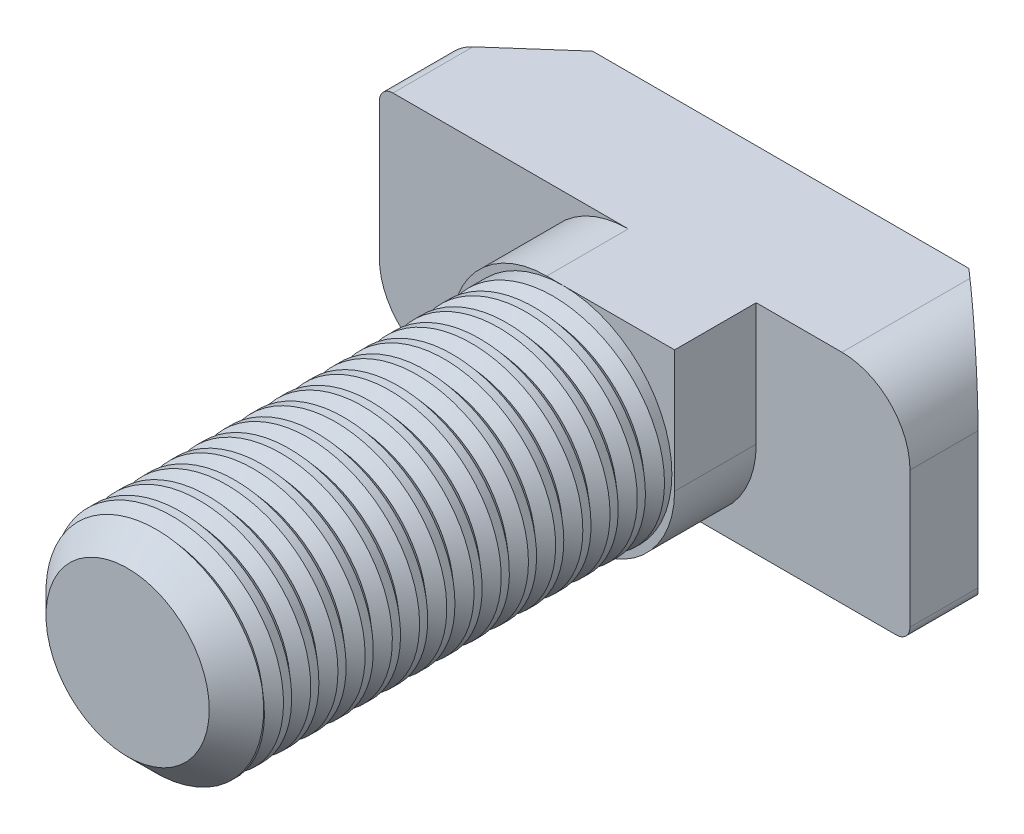
SolidWorks part; units mm, degrees
ref_plane "前视基准面" through (0, 0, 0) normal (0, 0, 1) x (1, 0, 0)
ref_plane "上视基准面" through (0, 0, 0) normal (0, 1, 0) x (1, 0, 0)
ref_plane "右视基准面" through (0, 0, 0) normal (1, 0, 0) x (0, 0, -1)
sketch "草图1" plane through (0, 0, 0) normal (0, 0, 1) x (1, 0, 0)
  line L1 (-9.75, -4) -> (9.75, -4)
  line L2 (-9.75, -4) -> (-9.75, 4)
  line L3 (-9.75, 4) -> (9.75, 4)
  line L4 (9.75, -4) -> (9.75, 4)
  line L5 (-9.75, -4) -> (9.75, 4) construction
  line L6 (-9.75, 4) -> (9.75, -4) construction
  point P0 (0, 0)
  dimension "D1" = 19.5
  dimension "D2" = 8
extrude "凸台-拉伸1" add sketch "草图1" along normal blind 5
fillet "圆角1" radius 2.5 2 edges at (9.75, 4, 2.5) (-9.75, -4, 2.5)
fillet "圆角2" radius 0.5 2 edges at (9.75, -4, 2.5) (-9.75, 4, 2.5)
sketch "草图2" plane through (0, -4, 0) normal (0, -1, 0) x (1, 0, 0)
  line L0 (-9.75, 2.5) -> (-6.9141, 0)
  line L1 (-9.75, 0) -> (-9.75, 5) construction
  line L2 (-7.25, 0) -> (9.25, 0) construction
  line L3 (-9.75, 2.5) -> (-9.75, 0)
  line L4 (-9.75, 0) -> (-6.9141, 0)
extrude "切除-拉伸2" cut sketch "草图2" against normal through all
mirror "镜向1" about plane through (0, 0, 0) normal (1, 0, 0) of "切除-拉伸2"
sketch "草图3" plane through (0, 0, 5) normal (0, 0, 1) x (1, 0, 0)
  line L0 (7.25, 4) -> (-9.25, 4) construction
  line L1 (-4.1, -4) -> (4.1, -4)
  line L2 (-4.1, -4) -> (-4.1, 4)
  line L3 (-4.1, 4) -> (4.1, 4)
  line L4 (4.1, -4) -> (4.1, 4)
  line L5 (-4.1, -4) -> (4.1, 4) construction
  line L6 (-4.1, 4) -> (4.1, -4) construction
  point P0 (0, 0)
  dimension "D1" = 8.2
extrude "凸台-拉伸2" add sketch "草图3" along normal blind 3
fillet "圆角3" radius 3.5 2 edges
sketch "草图4" plane through (0, 0, 8) normal (0, 0, 1) x (1, 0, 0)
  circle A0 centre (0, 0) radius 4
  dimension "D1" = 8
extrude "凸台-拉伸3" add sketch "草图4" along normal blind 16
chamfer "倒角1" distance 1 angle 45 1 edges at (4, 0, 24)
sketch "草图5" plane through (0, 0, 24) normal (0, 0, 1) x (1, 0, 0)
  circle A0 centre (0, 0) radius 4
curve "螺旋线/涡状线1" pitch 1 height 16 radius 4 centre (0, 0, 24) axis (0, 0, -1) start towards (-0.7071, 0.7071, 0)
sketch "草图6" plane through (0, 0, 0) normal (1, 0, 0) x (0, 0, -1)
  line L0 (-23.525, 4) -> (-24.225, 4)
  line L1 (-23.875, 4) -> (-23.875, 3.6) construction
  line L2 (-24.225, 4) -> (-23.875, 3.6)
  line L3 (-23.875, 3.6) -> (-23.525, 4)
  dimension "D1" = 0.7
  dimension "D2" = 0.4
sweep "切除-扫描1" cut profiles "草图6" path "螺旋线/涡状线1"
